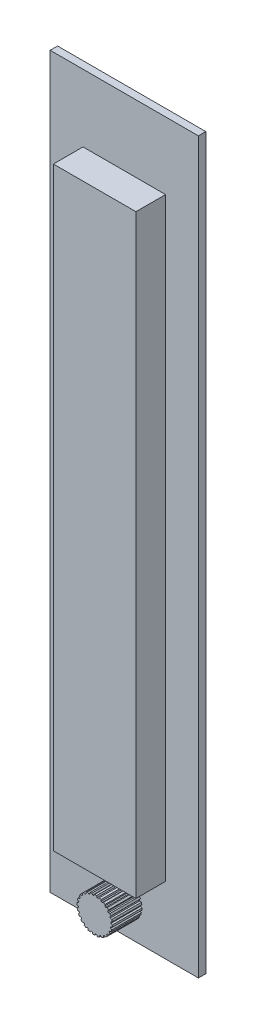
SolidWorks part; units mm, degrees
ref_plane "Front Plane" through (0, 0, 0) normal (0, 0, 1) x (1, 0, 0)
ref_plane "Top Plane" through (0, 0, 0) normal (0, 1, 0) x (1, 0, 0)
ref_plane "Right Plane" through (0, 0, 0) normal (1, 0, 0) x (0, 0, -1)
sketch "Sketch1" plane through (0, 0, 0) normal (0, 0, 1) x (1, 0, 0)
  line L1 (-25.4, -125) -> (25.4, -125)
  line L2 (-25.4, -125) -> (-25.4, 125)
  line L3 (-25.4, 125) -> (25.4, 125)
  line L4 (25.4, -125) -> (25.4, 125)
  line L5 (-25.4, -125) -> (25.4, 125) construction
  line L6 (-25.4, 125) -> (25.4, -125) construction
  line L7 (-14.1496, -101.9409) -> (14.1496, -101.9409)
  line L8 (-14.1496, -101.9409) -> (-14.1496, 101.9409)
  line L9 (-14.1496, 101.9409) -> (14.1496, 101.9409)
  line L10 (14.1496, -101.9409) -> (14.1496, 101.9409)
  line L11 (-14.1496, -101.9409) -> (14.1496, 101.9409) construction
  line L12 (-14.1496, 101.9409) -> (14.1496, -101.9409) construction
  circle A0 centre (0, -113.8738) radius 5.5736
  point P0 (0, 0)
  point P6 (0, 0)
  point P11 (0, -113.8738)
  dimension "D1" = 50.8
  dimension "D2" = 250
extrude "Boss-Extrude1" add sketch "Sketch1" along normal blind 2.54
extrude "Boss-Extrude2" add sketch "Sketch1<2>" along normal blind 12.7 contours L7 L10 L9 L8 region at (0, 0, 0)
sketch "Sketch1<2>" plane through (0, 0, 0) normal (0, 0, 1) x (1, 0, 0) same geometry as "Sketch1"
extrude "Boss-Extrude3" add sketch "Sketch1<3>" along normal blind 12.7 contours A0 region at (0, -113.8738, 0)
sketch "Sketch1<3>" plane through (0, 0, 0) normal (0, 0, 1) x (1, 0, 0) same geometry as "Sketch1"
sketch "Sketch2" plane through (0, 0, 12.7) normal (0, 0, 1) x (1, 0, 0)
  line L0 (-0.6655, -109.1112) -> (0, -107.8232)
  line L1 (0.6593, -107.8232) -> (1.0697, -109.1112)
  line L2 (1.0697, -109.1112) -> (-0.6655, -109.1112)
  line L3 (0, -107.8232) -> (0.6593, -107.8232)
extrude "Boss-Extrude4" add sketch "Sketch2" against normal blind 10.16
pattern_circular "CirPattern1" count 24 over 360 about axis through (0, -113.8738, 12.7) along (0, 0, -1) of "Boss-Extrude4"
